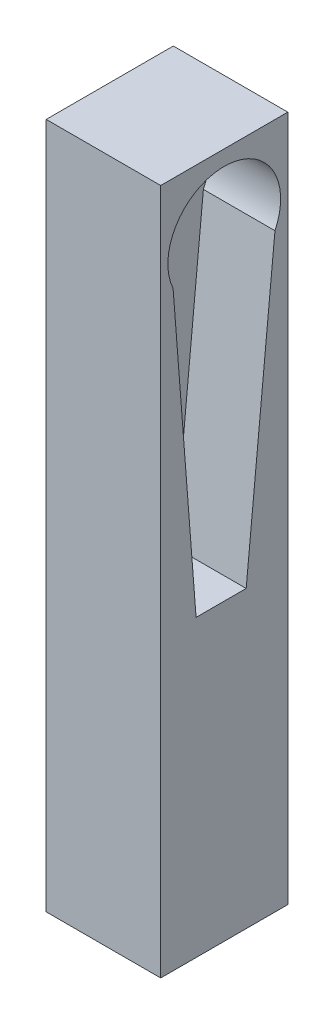
SolidWorks part; units mm, degrees
note: The reader was unsure of these and kept them because the rebuilt part matched: shared geometry of "Sketch1<3>".
ref_plane "Front Plane" through (0, 0, 0) normal (0, 0, 1) x (1, 0, 0)
ref_plane "Top Plane" through (0, 0, 0) normal (0, 1, 0) x (1, 0, 0)
ref_plane "Right Plane" through (0, 0, 0) normal (1, 0, 0) x (0, 0, -1)
sketch "Sketch1" plane through (0, 0, 0) normal (1, 0, 0) x (0, 0, -1)
  line L0 (114.5565, 367.603) -> (601.2232, 367.603) construction
  line L1 (-274.0854, -38.501) -> (212.5813, -38.501) construction
  line L2 (-3.5752, -1.6553) -> (-1.9683, -22.3642)
  line L3 (3.542, -1.7253) -> (1.5317, -22.3642)
  line L4 (1.5317, -22.3642) -> (-1.9683, -22.3642)
  line L5 (3.542, -1.7253) -> (-3.5752, -1.6553) construction
  line L6 (-3.5752, -1.6553) -> (-13.423, -1.6553) construction
  line L7 (3.542, -1.7253) -> (11.1127, -1.7253) construction
  line L8 (-4.1197, -1.6553) -> (-2.3124, -24.9468)
  line L9 (-2.3124, -24.9468) -> (1.8291, -24.9468)
  line L10 (1.8291, -24.9468) -> (4.0909, -1.7253)
  circle A0 centre (0, 0) radius 1.5
  arc A1 (-3.5752, -1.6553) -> (3.542, -1.7253) centre (0, 0) cw
  arc A2 (-4.1197, -1.6553) -> (4.0909, -1.7253) centre (0, 0) cw
  dimension "D1" = 3
  dimension "D2" = 0.5
  dimension "D3" = 85
  dimension "D4" = 85
  dimension "D5" = 3.5
extrude "Boss-Extrude1" add sketch "Sketch1" along normal blind 8 contours A2 L8 L9 L10 L2 A1 L3 L4
extrude "Boss-Extrude2" add sketch "Sketch1<3>" along normal blind 3 contours A1 L2 L4 L3 A0
sketch "Sketch1<3>" plane through (0, 0, 0) normal (1, 0, 0) x (0, 0, -1) same geometry as "Sketch1"
sketch "Sketch4" plane through (8, 0, 0) normal (1, 0, 0) x (0, 0, -1)
  line L1 (-4.4398, 5.0004) -> (4.4398, 5.0004)
  line L2 (-4.4398, 5.0004) -> (-4.4398, -42.9468)
  line L3 (-4.4398, -42.9468) -> (4.4398, -42.9468)
  line L4 (4.4398, 5.0004) -> (4.4398, -42.9468)
  line L5 (-4.1197, -1.6553) -> (-2.3124, -24.9468)
  line L6 (-2.3124, -24.9468) -> (1.8291, -24.9468)
  line L7 (-2.3124, -24.9468) -> (1.8291, -24.9468)
  line L9 (1.8291, -24.9468) -> (4.0909, -1.7253)
  line L10 (-4.1197, -1.6553) -> (-2.3124, -24.9468)
  line L14 (1.8291, -24.9468) -> (4.0909, -1.7253)
  arc A1 (4.0909, -1.7253) -> (-4.1197, -1.6553) centre (0, 0) ccw
  arc A2 (4.0909, -1.7253) -> (-4.1197, -1.6553) centre (0, 0) ccw
  point P11 (0, 0)
  point P12 (0, 0)
  dimension "D1" = 0
extrude "Boss-Extrude5" add sketch "Sketch4" against normal up to surface (8 mm away)
